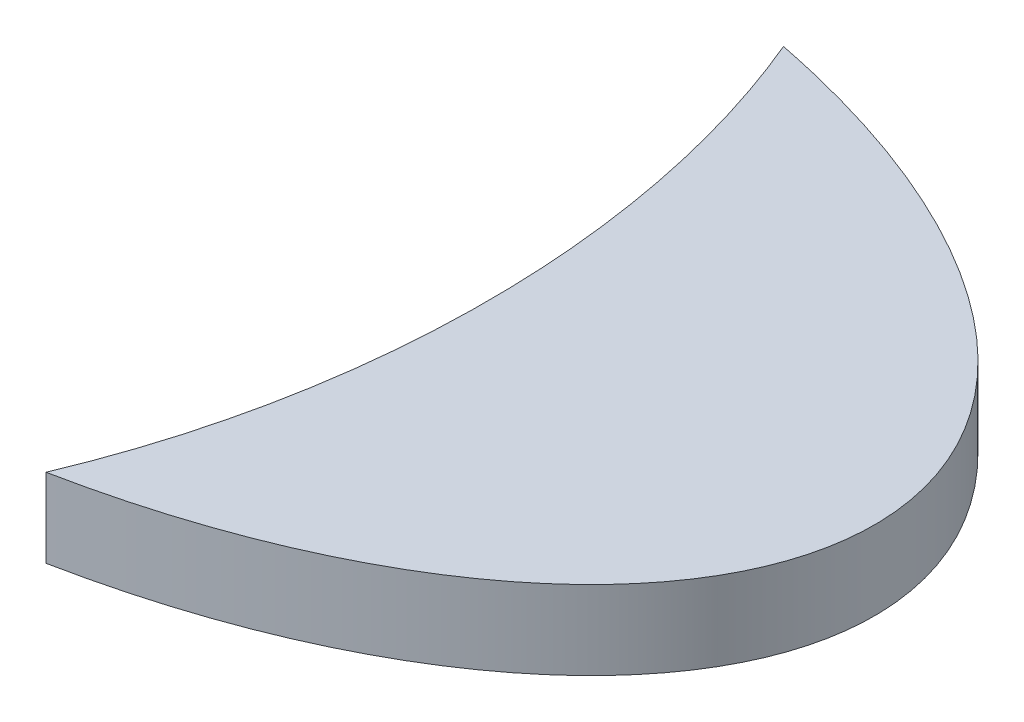
SolidWorks part; units mm, degrees
ref_plane "Front Plane" through (0, 0, 0) normal (0, 0, 1) x (1, 0, 0)
ref_plane "Top Plane" through (0, 0, 0) normal (0, 1, 0) x (1, 0, 0)
ref_plane "Right Plane" through (0, 0, 0) normal (1, 0, 0) x (0, 0, -1)
sketch "Sketch3" plane through (0, 0, 0) normal (0, 1, 0) x (1, 0, 0)
  ellipse E0 centre (0, 0) end of major axis (17.37, 0) minor radius 9.9
  ellipse E1 centre (-8.11, 0) end of major axis (-8.11, 19.88) minor radius 15.66
  point P7 (0, 0)
  point P14 (0, 0)
  point P15 (0, 0)
  dimension "D1" = 17.37
  dimension "D2" = 8.11
  dimension "D3" = 19.88
  dimension "D4" = 15.66
  dimension "D5" = 9.9
extrude "Boss-Extrude1" add sketch "Sketch3" along normal blind 2 contours E1 E0 region at (11.2402, 0, 0)
